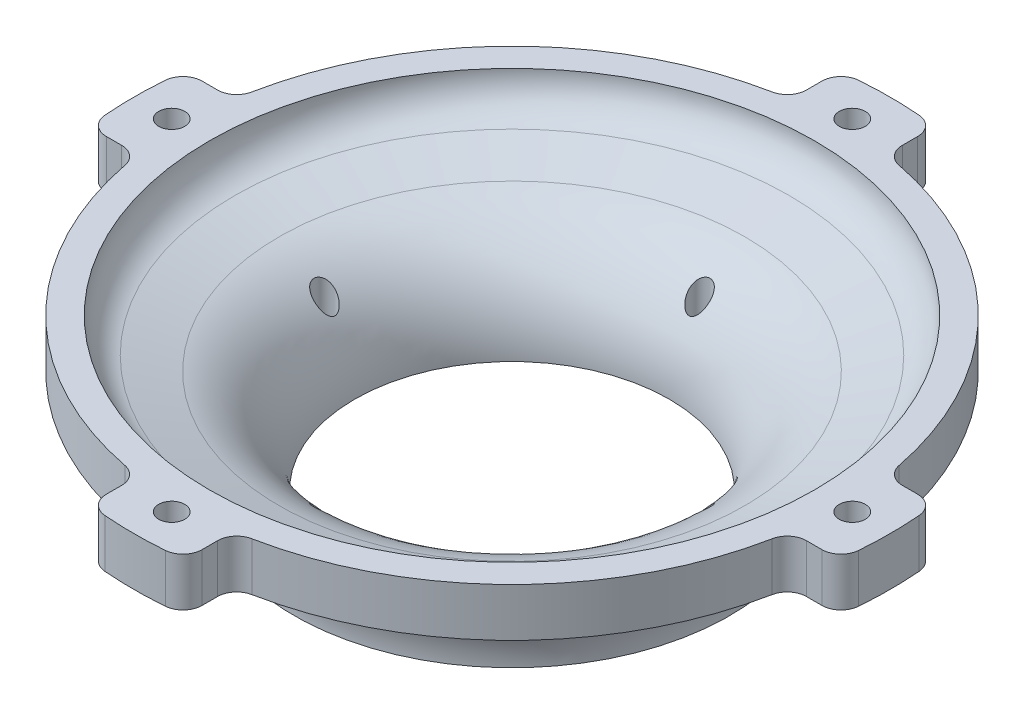
SolidWorks part; units mm, degrees
material "Nylon 101"
ref_plane "Front Plane" through (0, 0, 0) normal (0, 0, 1) x (1, 0, 0)
ref_plane "Top Plane" through (0, 0, 0) normal (0, 1, 0) x (1, 0, 0)
ref_plane "Right Plane" through (0, 0, 0) normal (1, 0, 0) x (0, 0, -1)
sketch "Sketch1" plane through (0, 0, 0) normal (0, 0, 1) x (1, 0, 0)
  line L0 (0, 0) -> (0, 25) construction
  line L1 (-62.5, 25) -> (-62.5, 17)
  line L2 (-62.5, 25) -> (-50, 25)
  line L3 (-45.7925, 19.2778) -> (-38.5, 17)
  line L4 (-62.5, 17) -> (-52.5, 17)
  line L5 (-26, 0) -> (-36, 0)
  line L6 (-26, 0) -> (-26, -8) construction
  line L7 (-50.6068, 16.7112) -> (-47.5962, 15.7708)
  line L8 (-36, 0) -> (-36, -8) construction
  arc A0 (-50, 25) -> (-45.7925, 19.2778) centre (-44.0052, 25) ccw
  arc A1 (-26, 0) -> (-38.5, 17) centre (-43.81, 0) ccw
  arc A2 (-52.5, 17) -> (-50.6068, 16.7112) centre (-52.5, 10.65) cw
  arc A3 (-47.5962, 15.7708) -> (-36, 0) centre (-52.5223, 0) cw
  dimension "D4" = 6.35
  dimension "D1" = 125
  dimension "D2" = 100
  dimension "D3" = 25
  dimension "D5" = 10
  dimension "D6" = 26
  dimension "D7" = 12.5
  dimension "D8" = 17
  dimension "D9" = 10
  dimension "D10" = 8
revolve "Revolve1" add sketch "Sketch1" angle 360 about L0
hole_wizard "#18 (0.1695) Diameter Hole1" positions "Sketch3" profile "Sketch4" hole size "#18" standard "ANSI Inch" end condition up to next
sketch "Sketch3" plane through (0, 25, 0) normal (0, 1, 0) x (1, 0, 0)
  line L0 (0, 50) -> (0, 62.5) construction
  line L2 (0, 56.25) -> (0, -56.25) construction
  line L4 (-56.25, 0) -> (56.25, 0) construction
  circle A0 centre (0, 0) radius 50 construction
  circle A1 centre (0, 0) radius 62.5 construction
  point P0 (0, 56.25)
  point P15 (0, -56.25)
  point P17 (-56.25, 0)
  point P18 (56.25, 0)
sketch "Sketch4" plane through (0, 25, -56.25) normal (1, 0, 0) x (0, 0, 1)
  line L0 (0, 0) -> (0, 8)
  line L1 (0, 8) -> (2.1526, 8)
  line L2 (2.1526, 8) -> (2.1526, 0)
  line L5 (2.1526, 0) -> (0, 0)
  line L11 (0, -6.35) -> (0, 107.95) construction
  dimension "Thru Hole Dia." = 4.3053
  dimension "Thru Hole Depth" = 8
hole_wizard "#8-32 Tapped Hole1" positions "Sketch6" profile "Sketch5" tap size "#8-32" standard "ANSI Inch" end condition up to next
sketch "Sketch6" plane through (0, 0, 0) normal (0, -1, 0) x (-1, 0, 0)
  line L0 (0, 26) -> (0, 36) construction
  line L1 (0, 31) -> (0, -31) construction
  line L3 (-31, 0) -> (31, 0) construction
  circle A0 centre (0, 0) radius 26 construction
  circle A2 centre (0, 0) radius 36 construction
  point P12 (0, 31)
  point P16 (0, -31)
  point P19 (-31, 0)
  point P20 (31, 0)
sketch "Sketch5" plane through (0, 0, -31) normal (1, 0, 0) x (0, 0, -1)
  line L0 (0, 0) -> (0, 12.3734)
  line L1 (0, 12.3734) -> (1.7272, 12.3734)
  line L2 (1.7272, 12.3734) -> (1.7272, 0)
  line L5 (1.7272, 0) -> (0, 0)
  line L11 (0, -6.35) -> (0, 107.95) construction
  dimension "Thread Major Dia." = 3.4544
  dimension "Thru Tap Drill Depth" = 12.3734
extrude "Cut-Extrude1" cut sketch "Sketch7" against normal blind 28
sketch "Sketch7" plane through (0, 44.9825, 0) normal (0, 1, 0) x (1, 0, 0)
  line L0 (0, 0) -> (0, 62.5) construction
  line L1 (0, 0) -> (-62.5, 0) construction
  line L2 (-44.1942, 44.1942) -> (-38.5373, 38.5373) construction
  line L3 (-56.5976, 7.921) -> (-59.1349, 7.921)
  line L4 (-7.921, 56.5976) -> (-7.921, 59.1349)
  line L5 (7.921, 56.5976) -> (7.921, 59.1349)
  line L6 (56.5976, 7.921) -> (59.1349, 7.921)
  line L7 (56.5976, -7.921) -> (59.1349, -7.921)
  line L8 (7.921, -56.5976) -> (7.921, -59.1349)
  line L9 (-7.921, -56.5976) -> (-7.921, -59.1349)
  line L10 (-56.5976, -7.921) -> (-59.1349, -7.921)
  arc A0 (-62.2997, 5) -> (-5, 62.2997) centre (0, 0) cw
  arc A2 (-53.4819, 10.4852) -> (-56.5976, 7.921) centre (-56.5976, 11.096) cw
  arc A3 (-10.4852, 53.4819) -> (-7.921, 56.5976) centre (-11.096, 56.5976) ccw
  arc A4 (-53.4819, 10.4852) -> (-10.4852, 53.4819) centre (0, 0) cw
  arc A5 (-7.921, 59.1349) -> (-5, 62.2997) centre (-4.746, 59.1349) cw
  arc A6 (-59.1349, 7.921) -> (-62.2997, 5) centre (-59.1349, 4.746) ccw
  arc A7 (5, 62.2997) -> (62.2997, 5) centre (0, 0) cw
  arc A8 (7.921, 59.1349) -> (5, 62.2997) centre (4.746, 59.1349) ccw
  arc A9 (10.4852, 53.4819) -> (7.921, 56.5976) centre (11.096, 56.5976) cw
  arc A10 (10.4852, 53.4819) -> (53.4819, 10.4852) centre (0, 0) cw
  arc A11 (53.4819, 10.4852) -> (56.5976, 7.921) centre (56.5976, 11.096) ccw
  arc A12 (59.1349, 7.921) -> (62.2997, 5) centre (59.1349, 4.746) cw
  arc A13 (62.2997, -5) -> (5, -62.2997) centre (0, 0) cw
  arc A14 (59.1349, -7.921) -> (62.2997, -5) centre (59.1349, -4.746) ccw
  arc A15 (53.4819, -10.4852) -> (56.5976, -7.921) centre (56.5976, -11.096) cw
  arc A16 (53.4819, -10.4852) -> (10.4852, -53.4819) centre (0, 0) cw
  arc A17 (10.4852, -53.4819) -> (7.921, -56.5976) centre (11.096, -56.5976) ccw
  arc A18 (7.921, -59.1349) -> (5, -62.2997) centre (4.746, -59.1349) cw
  arc A19 (-5, -62.2997) -> (-62.2997, -5) centre (0, 0) cw
  arc A20 (-7.921, -59.1349) -> (-5, -62.2997) centre (-4.746, -59.1349) ccw
  arc A21 (-10.4852, -53.4819) -> (-7.921, -56.5976) centre (-11.096, -56.5976) cw
  arc A22 (-10.4852, -53.4819) -> (-53.4819, -10.4852) centre (0, 0) cw
  arc A23 (-53.4819, -10.4852) -> (-56.5976, -7.921) centre (-56.5976, -11.096) ccw
  arc A24 (-59.1349, -7.921) -> (-62.2997, -5) centre (-59.1349, -4.746) cw
  point P60 (0, 0)
